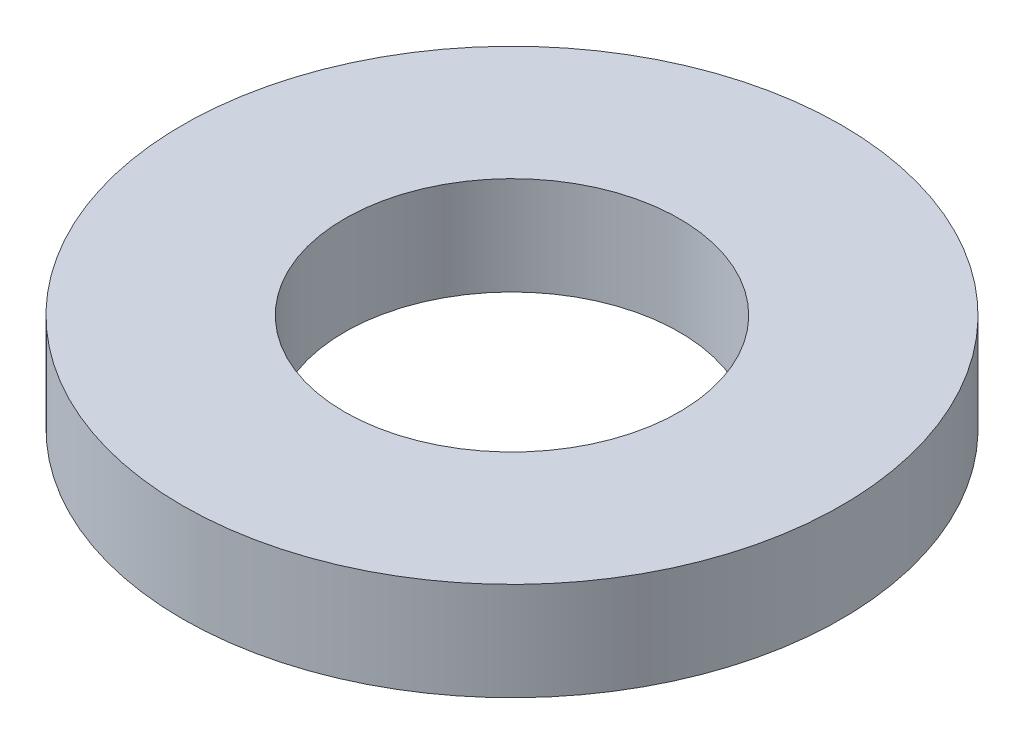
SolidWorks part; units mm, degrees
ref_plane "Front Plane" through (0, 0, 0) normal (0, 0, 1) x (1, 0, 0)
ref_plane "Top Plane" through (0, 0, 0) normal (0, 1, 0) x (1, 0, 0)
ref_plane "Right Plane" through (0, 0, 0) normal (1, 0, 0) x (0, 0, -1)
sketch "Sketch1" plane through (0, 0, 0) normal (0, 1, 0) x (1, 0, 0)
  circle A0 centre (0, 0) radius 6.35
  arc A4 (2.2922, 5.9218) -> (-4.4275, -4.5518) centre (0, 0) ccw construction
  circle A5 centre (0, 0) radius 3.2258
  circle A6 centre (0, 0) radius 3.2258
  dimension "D1" = 0.0508
extrude "Boss-Extrude1" add sketch "Sketch1" along normal up to surface (1.8914 mm away)
